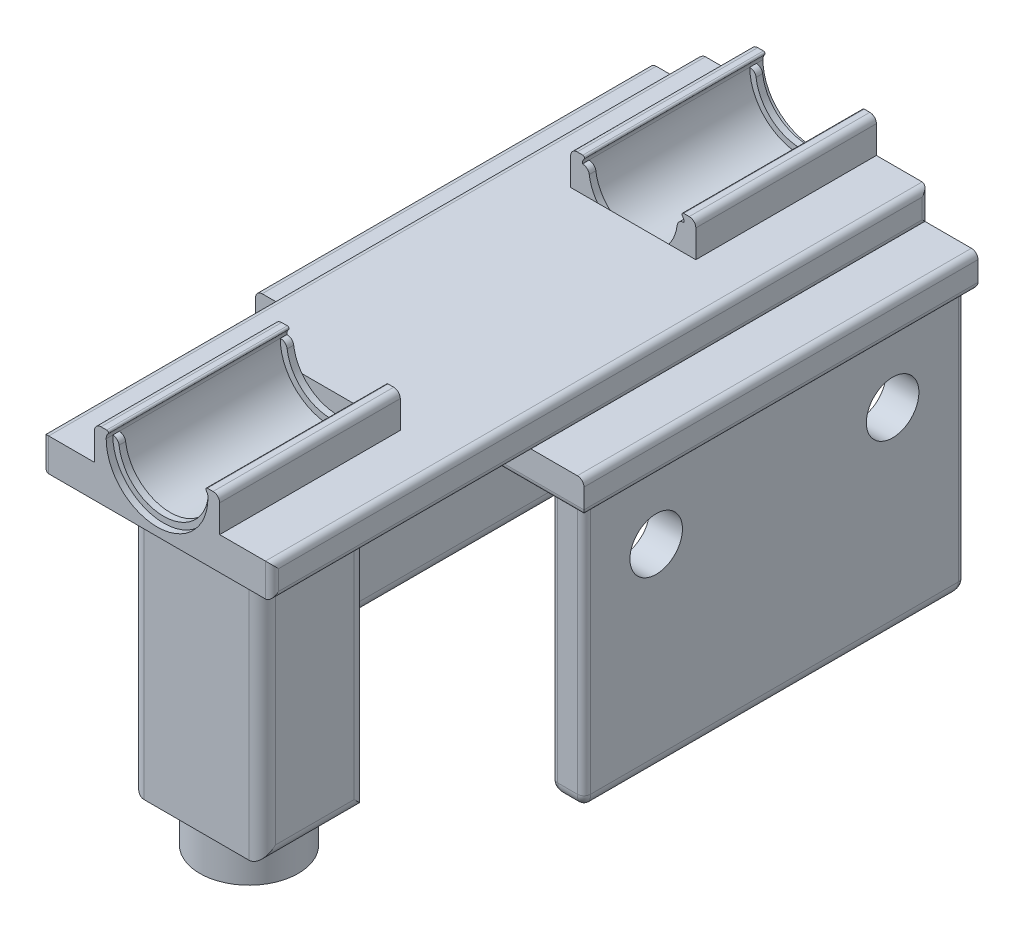
SolidWorks part; units mm, degrees
ref_plane "Front Plane" through (0, 0, 0) normal (0, 0, 1) x (1, 0, 0)
ref_plane "Top Plane" through (0, 0, 0) normal (0, 1, 0) x (1, 0, 0)
ref_plane "Right Plane" through (0, 0, 0) normal (1, 0, 0) x (0, 0, -1)
sketch "Sketch1" plane through (0, 0, 0) normal (0, 1, 0) x (1, 0, 0)
  line L1 (-17.5, -50) -> (17.5, -50)
  line L2 (-17.5, -50) -> (-17.5, 50)
  line L3 (-17.5, 50) -> (17.5, 50)
  line L4 (17.5, -50) -> (17.5, 50)
  line L5 (-17.5, -50) -> (17.5, 50) construction
  line L6 (-17.5, 50) -> (17.5, -50) construction
  point P0 (0, 0)
  dimension "D1" = 100
  dimension "D2" = 35
extrude "Boss-Extrude1" add sketch "Sketch1" along normal blind 5
sketch "Sketch2" plane through (0, 0, 50) normal (0, 0, 1) x (1, 0, 0)
  line L0 (0, -2.75) -> (0, 2.75) construction
  line L1 (-7.6705, 10.1905) -> (-8.5308, 10.1905)
  line L2 (-9.5308, 9.1905) -> (-9.5308, 0)
  line L3 (-17.5, 0) -> (17.5, 0) construction
  line L4 (9.5308, 9.1905) -> (9.5308, 0)
  line L5 (7.6705, 10.1905) -> (8.5308, 10.1905)
  line L6 (-9.5308, 0) -> (9.5308, 0)
  arc A0 (-7.75, 9) -> (7.75, 9) centre (0, 9) ccw
  arc A1 (-7.75, 9) -> (-7.4751, 9.7845) centre (-6.493, 9) cw
  arc A2 (7.75, 9) -> (7.4751, 9.7845) centre (6.493, 9) ccw
  arc A3 (-7.4751, 9.7845) -> (-7.6705, 10.1905) centre (-7.6705, 9.9405) ccw
  arc A4 (7.4751, 9.7845) -> (7.6705, 10.1905) centre (7.6705, 9.9405) cw
  arc A5 (9.5308, 9.1905) -> (8.5308, 10.1905) centre (8.5308, 9.1905) ccw
  arc A6 (-8.5308, 10.1905) -> (-9.5308, 9.1905) centre (-8.5308, 9.1905) ccw
  point P18 (-6.8964, 10.1905)
  point P21 (6.8964, 10.1905)
  point P24 (9.5308, 10.1905)
  point P27 (-9.5308, 10.1905)
  dimension "D1" = 7.75
  dimension "D3" = 0.25
  dimension "D4" = 0.25
  dimension "D5" = 1
  dimension "D2" = 9
extrude "Boss-Extrude2" add sketch "Sketch2" against normal blind 27.5
mirror "Mirror1" about plane through (0, 0, 0) normal (0, 0, 1) of "Boss-Extrude2"
ref_plane "Plane1" through (0, 0, 48) normal (0, 0, 1) x (1, 0, 0)
sketch "Sketch3" plane through (0, 0, 48) normal (0, 0, 1) x (1, 0, 0)
  line L0 (-7.75, 9) -> (7.75, 9)
  arc A0 (-7.75, 9) -> (7.75, 9) centre (0, 9) ccw
  dimension "D1" = 9
extrude "Cut-Extrude1" cut sketch "Sketch3" against normal blind 25.5 and the other way blind 2
sketch "Sketch4" plane through (0, 0, 48) normal (0, 0, 1) x (1, 0, 0)
  line L0 (-7.75, 9) -> (-6.8477, 9)
  line L1 (6.8477, 9) -> (7.75, 9)
  arc A1 (7.75, 9) -> (-7.75, 9) centre (0, 9) cw
  arc A2 (6.8477, 9) -> (-6.8477, 9) centre (0, 9) cw
  dimension "D1" = 9
extrude "Boss-Extrude3" add sketch "Sketch4" along normal blind 1
ref_plane "Plane2" through (0, 0, 23.5) normal (0, 0, 1) x (1, 0, 0)
sketch "Sketch5" plane through (0, 0, 23.5) normal (0, 0, 1) x (1, 0, 0)
  line L0 (-7.75, 9) -> (-6.75, 9)
  line L1 (6.75, 9) -> (7.75, 9)
  arc A0 (7.75, 9) -> (-7.75, 9) centre (0, 9) cw
  arc A1 (-7.75, 9) -> (7.75, 9) centre (0, 9) ccw construction
  arc A2 (-7.75, 9) -> (7.75, 9) centre (0, 9) ccw construction
  arc A4 (6.75, 9) -> (-6.75, 9) centre (0, 9) cw
  dimension "D1" = 9
  dimension "D2" = 1
extrude "Boss-Extrude4" add sketch "Sketch5" against normal blind 1
fillet "Fillet1" radius 1 4 edges at (6.8477, 9, 48.5) (6.75, 9, 23) (-6.75, 9, 23) (-6.8477, 9, 48.5)
mirror "Mirror2" about plane through (0, 0, 0) normal (0, 0, 1) of "Fillet1", "Boss-Extrude4", "Boss-Extrude3", "Cut-Extrude1"
fillet "Fillet2" radius 1 8 edges at (-17.5, 2.5, -50) (-17.5, 5, 0) (-17.5, 2.5, 50) (-17.5, 0, 0) (17.5, 2.5, 50) (17.5, 5, 0) (17.5, 2.5, -50) (17.5, 0, 0)
sketch "Sketch6" plane through (0, 0, 0) normal (0, -1, 0) x (1, 0, 0)
  line L0 (16.5, -50) -> (-16.5, -50) construction
  line L1 (-25, -50) -> (25, -50)
  line L2 (-25, -50) -> (-25, 10)
  line L3 (-25, 10) -> (25, 10)
  line L4 (25, -50) -> (25, 10)
  line L5 (-25, -50) -> (25, 10) construction
  line L6 (-25, 10) -> (25, -50) construction
  point P0 (0, 0)
  point P9 (0, -20)
  dimension "D1" = 50
  dimension "D2" = 60
extrude "Boss-Extrude5" add sketch "Sketch6" along normal blind 5
fillet "Fillet3" radius 1 6 edges at (25, -5, -20) (0, -5, 10) (-25, -5, -20) (0, -5, -50) (25, 0, -20) (-25, 0, -20)
fillet "Fillet4" [suppressed] radius 1
sketch "Sketch7" plane through (0, -5, 0) normal (0, -1, 0) x (1, 0, 0)
  line L0 (-24, -49) -> (24, -49) construction
  line L1 (-24, 9) -> (-19, 9)
  line L2 (-24, 9) -> (-24, -49)
  line L3 (-24, -49) -> (-19, -49)
  line L4 (-19, 9) -> (-19, -49)
  line L6 (24, 9) -> (19, 9)
  line L7 (24, 9) -> (24, -49)
  line L8 (24, -49) -> (19, -49)
  line L9 (19, 9) -> (19, -49)
  dimension "D1" = 5
extrude "Boss-Extrude6" add sketch "Sketch7" along normal blind 40
fillet "Fillet5" radius 2 8 edges at (21.5, -45, -49) (19, -45, -20) (21.5, -45, 9) (24, -45, -20) (-21.5, -45, 9) (-19, -45, -20) (-21.5, -45, -49) (-24, -45, -20)
fillet "Fillet6" radius 1 16 edges at (-23.4142, -44.4142, 8.4142) (-19.5858, -44.4142, 8.4142) (19.5858, -44.4142, 8.4142) (23.4142, -44.4142, 8.4142) (23.4142, -44.4142, -48.4142) (19.5858, -44.4142, -48.4142) (-19.5858, -44.4142, -48.4142) (-23.4142, -44.4142, -48.4142) (-24, -24, 9) (-19, -24, 9) (19, -24, 9) (24, -24, 9) (24, -24, -49) (19, -24, -49) (-19, -24, -49) (-24, -24, -49)
sketch "Sketch8" plane through (-24, 0, 0) normal (-1, 0, 0) x (0, 0, 1)
  line L0 (-50, 0) -> (10, 0) construction
  line L2 (-48, -5) -> (-48, -43) construction
  circle A0 centre (-38, -15) radius 4
  circle A2 centre (-2, -15) radius 4
  dimension "D2" = 8
  dimension "D1" = 15
  dimension "D3" = 10
  dimension "D4" = 36
extrude "Cut-Extrude2" cut sketch "Sketch8" against normal through all
sketch "Sketch9" plane through (0, 0, 0) normal (0, -1, 0) x (1, 0, 0)
  line L0 (-16.5, 50) -> (16.5, 50) construction
  line L1 (-10, 28) -> (10, 28)
  line L2 (-10, 28) -> (-10, 44)
  line L3 (-10, 44) -> (10, 44)
  line L4 (10, 28) -> (10, 44)
  point P4 (0, 28)
  dimension "D1" = 20
  dimension "D2" = 16
  dimension "D3" = 6
extrude "Boss-Extrude7" add sketch "Sketch9" along normal blind 41.7
sketch "Sketch12" plane through (0, -41.7, 0) normal (0, -1, 0) x (1, 0, 0)
  line L0 (10, 28) -> (10, 44) construction
  circle A0 centre (0, 36) radius 7.5
  point P4 (10, 36)
  dimension "D1" = 15
extrude "Boss-Extrude9" add sketch "Sketch12" along normal blind 6
sketch "Sketch13" plane through (0, -47.7, 0) normal (0, -1, 0) x (1, 0, 0)
  circle A0 centre (0, 36) radius 1.5
  dimension "D1" = 3
extrude "Cut-Extrude4" cut sketch "Sketch13" against normal blind 10
fillet "Fillet8" radius 2 10 edges at (-10, 0, 36) (0, 0, 28) (0, 0, 44) (10, 0, 36) (10, -20.85, 28) (10, -41.7, 36) (10, -20.85, 44) (-10, -20.85, 28) (-10, -41.7, 36) (-10, -20.85, 44)
